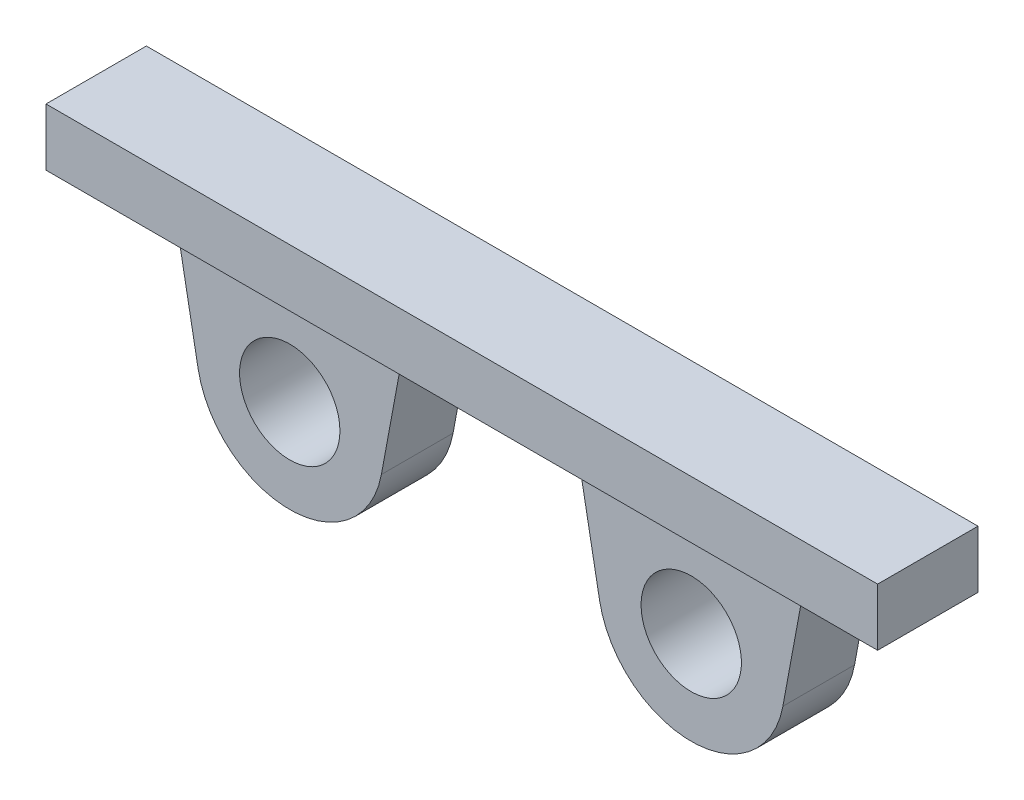
SolidWorks part; units mm, degrees
ref_plane "前视基准面" through (0, 0, 0) normal (0, 0, 1) x (1, 0, 0)
ref_plane "上视基准面" through (0, 0, 0) normal (0, 1, 0) x (1, 0, 0)
ref_plane "右视基准面" through (0, 0, 0) normal (1, 0, 0) x (0, 0, -1)
sketch "草图1" plane through (0, 0, 0) normal (0, 0, 1) x (1, 0, 0)
  line L0 (-7.6087, -1.184) -> (-6, 7.5)
  line L1 (-6, 7.5) -> (6, 7.5)
  line L2 (0, -5.4665) -> (0, 26.2423) construction
  line L3 (29, 11.5) -> (-29, 11.5)
  line L4 (-29, 11.5) -> (-29, 7.5)
  line L5 (-29, 7.5) -> (-22, 7.5)
  line L6 (-22, 7.5) -> (-20.3913, -1.184)
  line L7 (-14, 0) -> (-14, 24.4406) construction
  line L8 (-42.0038, 0) -> (42.8871, 0) construction
  line L9 (14, 0) -> (14, 24.4406) construction
  line L10 (22, 7.5) -> (20.3913, -1.184)
  line L11 (29, 7.5) -> (22, 7.5)
  line L12 (29, 11.5) -> (29, 7.5)
  line L13 (7.6087, -1.184) -> (6, 7.5)
  circle A0 centre (-14, 0) radius 3.5
  arc A1 (-20.3913, -1.184) -> (-7.6087, -1.184) centre (-14, 0) ccw
  arc A2 (20.3913, -1.184) -> (7.6087, -1.184) centre (14, 0) cw
  circle A3 centre (14, 0) radius 3.5
  point P21 (0, 7.5)
  point P22 (0, 11.5)
  dimension "D1" = 3.5
  dimension "D2" = 6.5
  dimension "D3" = 15
  dimension "D4" = 7
  dimension "D5" = 11.5
  dimension "D6" = 4
  dimension "D7" = 28
extrude "凸台-拉伸1" add sketch "草图1" along normal blind 5
sketch "草图2" plane through (0, 7.5, 0) normal (0, -1, 0) x (1, 0, 0)
  line L0 (-29, 5) -> (-29, 0) construction
  line L1 (29, 5) -> (-29, 5)
  line L2 (29, 5) -> (29, 7)
  line L3 (29, 7) -> (-29, 7)
  line L4 (-29, 5) -> (-29, 7)
  dimension "D1" = 2
extrude "凸台-拉伸2" add sketch "草图2" against normal up to surface (4 mm away) up to face at (0, 11.5, 2.5)
ref_axis "基准轴1" through (14, 0, 5) along (0, 0, -1)
